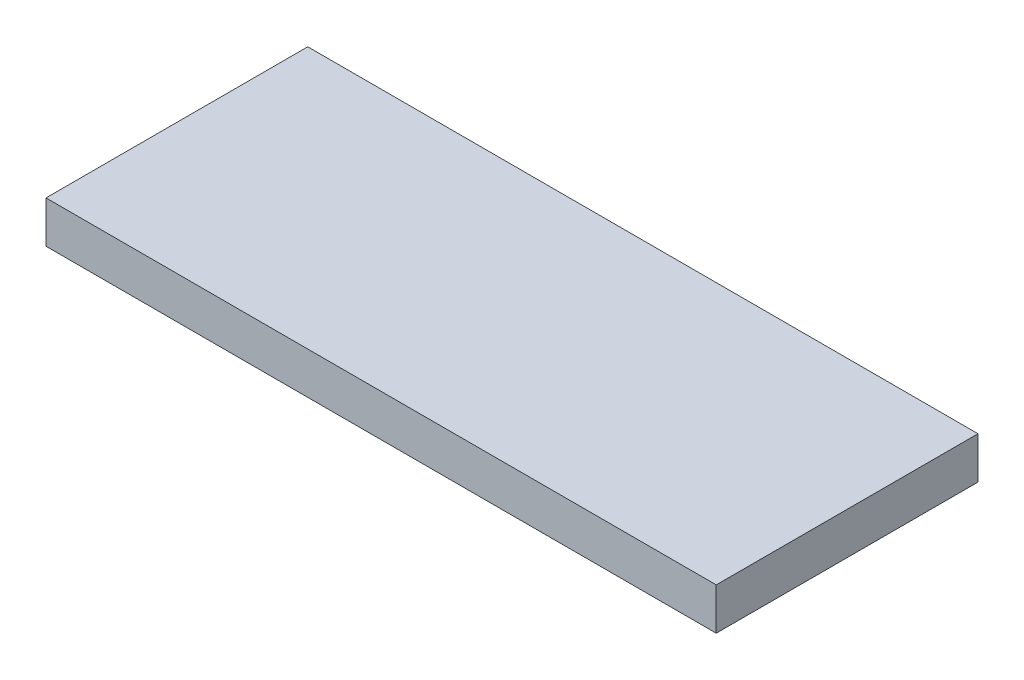
SolidWorks part; units mm, degrees
ref_plane "Front Plane" through (0, 0, 0) normal (0, 0, 1) x (1, 0, 0)
ref_plane "Top Plane" through (0, 0, 0) normal (0, 1, 0) x (1, 0, 0)
ref_plane "Right Plane" through (0, 0, 0) normal (1, 0, 0) x (0, 0, -1)
sketch "Sketch1" plane through (0, 0, 0) normal (0, 1, 0) x (1, 0, 0)
  line L1 (0, 0) -> (32.0076, 0)
  line L2 (0, 0) -> (0, 12.5)
  line L3 (0, 12.5) -> (32.0076, 12.5)
  line L4 (32.0076, 0) -> (32.0076, 12.5)
  dimension "D1" = 12.5
extrude "Boss-Extrude1" add sketch "Sketch1" along normal blind 2
